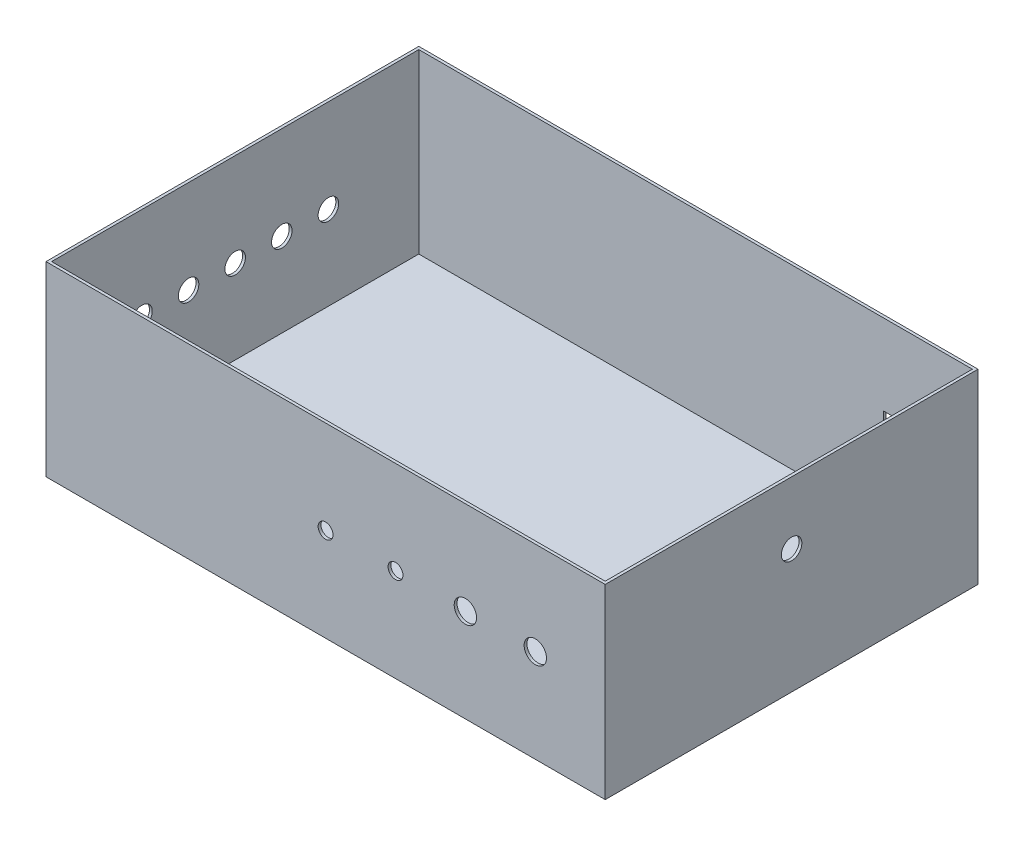
SolidWorks part; units mm, degrees
ref_plane "Płaszczyzna przednia" through (0, 0, 0) normal (0, 0, 1) x (1, 0, 0)
ref_plane "Płaszczyzna górna" through (0, 0, 0) normal (0, 1, 0) x (1, 0, 0)
ref_plane "Płaszczyzna prawa" through (0, 0, 0) normal (1, 0, 0) x (0, 0, -1)
sketch "Sketch1" plane through (0, 0, 0) normal (0, 1, 0) x (1, 0, 0)
  line L1 (-300, -200) -> (300, -200)
  line L2 (-300, -200) -> (-300, 200)
  line L3 (-300, 200) -> (300, 200)
  line L4 (300, -200) -> (300, 200)
  line L5 (-300, -200) -> (300, 200) construction
  line L6 (-300, 200) -> (300, -200) construction
  point P0 (0, 0)
  dimension "D1" = 600
  dimension "D2" = 400
extrude "Boss-Extrude1" add sketch "Sketch1" along normal blind 200
sketch "Sketch2" plane through (0, 200, 0) normal (0, 1, 0) x (1, 0, 0)
  line L1 (-297, -197) -> (297, -197)
  line L2 (-297, -197) -> (-297, 197)
  line L3 (-297, 197) -> (297, 197)
  line L4 (297, -197) -> (297, 197)
  line L5 (-297, -197) -> (297, 197) construction
  line L6 (-297, 197) -> (297, -197) construction
  point P0 (0, 0)
  dimension "D1" = 594
  dimension "D2" = 394
extrude "Cut-Extrude1" cut sketch "Sketch2" against normal blind 190
sketch "Sketch3" plane through (-300, 0, 0) normal (-1, 0, 0) x (0, 0, 1)
  line L0 (-200, 100) -> (200, 100) construction
  line L1 (-200, 200) -> (-200, 0) construction
  line L2 (200, 200) -> (200, 0) construction
  line L3 (-200, 100) -> (0, 100) construction
  line L4 (0, 100) -> (-50, 100) construction
  line L5 (-50, 100) -> (-100, 100) construction
  line L6 (0, 100) -> (50, 100) construction
  line L7 (50, 100) -> (100, 100) construction
  circle A0 centre (-100, 100) radius 11
  circle A1 centre (-50, 100) radius 11
  circle A2 centre (50, 100) radius 11
  circle A3 centre (100, 100) radius 11
  circle A4 centre (0, 100) radius 11
  dimension "D1" = 50
  dimension "D2" = 50
  dimension "D3" = 50
  dimension "D4" = 50
extrude "Cut-Extrude2" cut sketch "Sketch3" against normal blind 10
sketch "Sketch4" plane through (0, 0, 200) normal (0, 0, 1) x (1, 0, 0)
  line L0 (300, 100) -> (-300, 100) construction
  line L1 (300, 200) -> (300, 0) construction
  line L2 (-300, 200) -> (-300, 0) construction
  line L3 (0, 100) -> (75, 100) construction
  line L4 (75, 100) -> (150, 100) construction
  line L5 (150, 100) -> (225, 100) construction
  circle A0 centre (150, 100) radius 12
  circle A1 centre (75, 100) radius 8
  circle A2 centre (225, 100) radius 12
  circle A3 centre (0, 100) radius 8
  dimension "D3" = 75
  dimension "D1" = 75
  dimension "D2" = 75
extrude "Cut-Extrude3" cut sketch "Sketch4" against normal blind 10
sketch "Sketch5" plane through (0, 0, -200) normal (0, 0, -1) x (-1, 0, 0)
  line L0 (-300, 100) -> (300, 100) construction
  line L1 (-300, 200) -> (-300, 0) construction
  line L2 (300, 200) -> (300, 0) construction
  line L3 (-300, 100) -> (-225, 100) construction
  line L5 (-248.5, 86.5) -> (-201.5, 86.5)
  line L6 (-248.5, 86.5) -> (-248.5, 113.5)
  line L7 (-248.5, 113.5) -> (-201.5, 113.5)
  line L8 (-201.5, 86.5) -> (-201.5, 113.5)
  line L9 (-248.5, 86.5) -> (-201.5, 113.5) construction
  line L10 (-248.5, 113.5) -> (-201.5, 86.5) construction
  dimension "D1" = 75
  dimension "D2" = 27
  dimension "D3" = 47
extrude "Cut-Extrude4" cut sketch "Sketch5" against normal blind 10
sketch "Sketch6" plane through (300, 0, 0) normal (1, 0, 0) x (0, 0, -1)
  line L0 (-200, 100) -> (200, 100) construction
  line L1 (-200, 200) -> (-200, 0) construction
  line L2 (200, 200) -> (200, 0) construction
  line L3 (0, 0) -> (0, 100) construction
  line L4 (0, 100) -> (0, 200) construction
  line L5 (-200, 200) -> (200, 200) construction
  line L6 (0, 100) -> (0, 133) construction
  circle A0 centre (0, 133) radius 11
  dimension "D1" = 33
extrude "Cut-Extrude5" cut sketch "Sketch6" against normal blind 10
